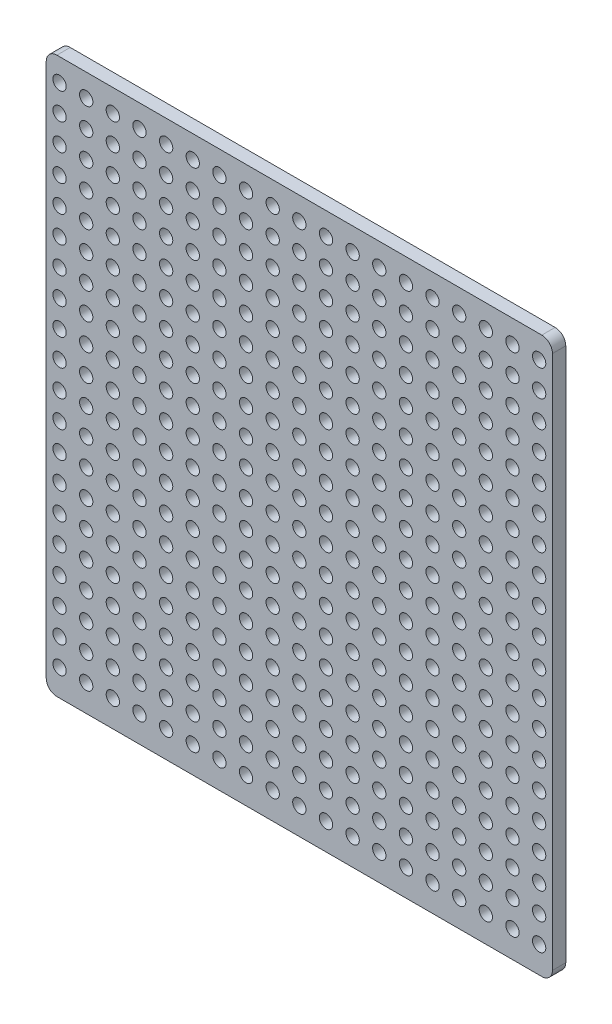
SolidWorks part; units mm, degrees
ref_plane "Front Plane" through (0, 0, 0) normal (0, 0, 1) x (1, 0, 0)
ref_plane "Top Plane" through (0, 0, 0) normal (0, 1, 0) x (1, 0, 0)
ref_plane "Right Plane" through (0, 0, 0) normal (1, 0, 0) x (0, 0, -1)
sketch "Sketch1" plane through (0, 0, 0) normal (0, 0, 1) x (1, 0, 0)
  line L1 (0, 0) -> (190, 0)
  line L2 (0, 0) -> (0, 208.5)
  line L3 (0, 208.5) -> (190, 208.5)
  line L4 (190, 0) -> (190, 208.5)
  circle A1 centre (5, 10) radius 2.5
  circle A2 centre (15, 10) radius 2.5
  circle A3 centre (25, 10) radius 2.5
  circle A4 centre (35, 10) radius 2.5
  circle A5 centre (45, 10) radius 2.5
  circle A6 centre (55, 10) radius 2.5
  circle A7 centre (65, 10) radius 2.5
  circle A8 centre (75, 10) radius 2.5
  circle A9 centre (85, 10) radius 2.5
  circle A10 centre (95, 10) radius 2.5
  circle A11 centre (105, 10) radius 2.5
  circle A12 centre (115, 10) radius 2.5
  circle A13 centre (125, 10) radius 2.5
  circle A14 centre (135, 10) radius 2.5
  circle A15 centre (145, 10) radius 2.5
  circle A16 centre (155, 10) radius 2.5
  circle A17 centre (165, 10) radius 2.5
  circle A18 centre (175, 10) radius 2.5
  circle A19 centre (185, 10) radius 2.5
  circle A21 centre (15, 20) radius 2.5
  circle A22 centre (25, 20) radius 2.5
  circle A23 centre (35, 20) radius 2.5
  circle A24 centre (45, 20) radius 2.5
  circle A25 centre (55, 20) radius 2.5
  circle A26 centre (65, 20) radius 2.5
  circle A27 centre (75, 20) radius 2.5
  circle A28 centre (85, 20) radius 2.5
  circle A29 centre (95, 20) radius 2.5
  circle A30 centre (105, 20) radius 2.5
  circle A31 centre (115, 20) radius 2.5
  circle A32 centre (125, 20) radius 2.5
  circle A33 centre (135, 20) radius 2.5
  circle A34 centre (145, 20) radius 2.5
  circle A35 centre (155, 20) radius 2.5
  circle A36 centre (165, 20) radius 2.5
  circle A37 centre (175, 20) radius 2.5
  circle A38 centre (185, 20) radius 2.5
  circle A40 centre (15, 30) radius 2.5
  circle A41 centre (25, 30) radius 2.5
  circle A42 centre (35, 30) radius 2.5
  circle A43 centre (45, 30) radius 2.5
  circle A44 centre (55, 30) radius 2.5
  circle A45 centre (65, 30) radius 2.5
  circle A46 centre (75, 30) radius 2.5
  circle A47 centre (85, 30) radius 2.5
  circle A48 centre (95, 30) radius 2.5
  circle A49 centre (105, 30) radius 2.5
  circle A50 centre (115, 30) radius 2.5
  circle A51 centre (125, 30) radius 2.5
  circle A52 centre (135, 30) radius 2.5
  circle A53 centre (145, 30) radius 2.5
  circle A54 centre (155, 30) radius 2.5
  circle A55 centre (165, 30) radius 2.5
  circle A56 centre (175, 30) radius 2.5
  circle A57 centre (185, 30) radius 2.5
  circle A59 centre (15, 40) radius 2.5
  circle A60 centre (25, 40) radius 2.5
  circle A61 centre (35, 40) radius 2.5
  circle A62 centre (45, 40) radius 2.5
  circle A63 centre (55, 40) radius 2.5
  circle A64 centre (65, 40) radius 2.5
  circle A65 centre (75, 40) radius 2.5
  circle A66 centre (85, 40) radius 2.5
  circle A67 centre (95, 40) radius 2.5
  circle A68 centre (105, 40) radius 2.5
  circle A69 centre (115, 40) radius 2.5
  circle A70 centre (125, 40) radius 2.5
  circle A71 centre (135, 40) radius 2.5
  circle A72 centre (145, 40) radius 2.5
  circle A73 centre (155, 40) radius 2.5
  circle A74 centre (165, 40) radius 2.5
  circle A75 centre (175, 40) radius 2.5
  circle A76 centre (185, 40) radius 2.5
  circle A78 centre (15, 50) radius 2.5
  circle A79 centre (25, 50) radius 2.5
  circle A80 centre (35, 50) radius 2.5
  circle A81 centre (45, 50) radius 2.5
  circle A82 centre (55, 50) radius 2.5
  circle A83 centre (65, 50) radius 2.5
  circle A84 centre (75, 50) radius 2.5
  circle A85 centre (85, 50) radius 2.5
  circle A86 centre (95, 50) radius 2.5
  circle A87 centre (105, 50) radius 2.5
  circle A88 centre (115, 50) radius 2.5
  circle A89 centre (125, 50) radius 2.5
  circle A90 centre (135, 50) radius 2.5
  circle A91 centre (145, 50) radius 2.5
  circle A92 centre (155, 50) radius 2.5
  circle A93 centre (165, 50) radius 2.5
  circle A94 centre (175, 50) radius 2.5
  circle A95 centre (185, 50) radius 2.5
  circle A97 centre (15, 60) radius 2.5
  circle A98 centre (25, 60) radius 2.5
  circle A99 centre (35, 60) radius 2.5
  circle A100 centre (45, 60) radius 2.5
  circle A101 centre (55, 60) radius 2.5
  circle A102 centre (65, 60) radius 2.5
  circle A103 centre (75, 60) radius 2.5
  circle A104 centre (85, 60) radius 2.5
  circle A105 centre (95, 60) radius 2.5
  circle A106 centre (105, 60) radius 2.5
  circle A107 centre (115, 60) radius 2.5
  circle A108 centre (125, 60) radius 2.5
  circle A109 centre (135, 60) radius 2.5
  circle A110 centre (145, 60) radius 2.5
  circle A111 centre (155, 60) radius 2.5
  circle A112 centre (165, 60) radius 2.5
  circle A113 centre (175, 60) radius 2.5
  circle A114 centre (185, 60) radius 2.5
  circle A116 centre (15, 70) radius 2.5
  circle A117 centre (25, 70) radius 2.5
  circle A118 centre (35, 70) radius 2.5
  circle A119 centre (45, 70) radius 2.5
  circle A120 centre (55, 70) radius 2.5
  circle A121 centre (65, 70) radius 2.5
  circle A122 centre (75, 70) radius 2.5
  circle A123 centre (85, 70) radius 2.5
  circle A124 centre (95, 70) radius 2.5
  circle A125 centre (105, 70) radius 2.5
  circle A126 centre (115, 70) radius 2.5
  circle A127 centre (125, 70) radius 2.5
  circle A128 centre (135, 70) radius 2.5
  circle A129 centre (145, 70) radius 2.5
  circle A130 centre (155, 70) radius 2.5
  circle A131 centre (165, 70) radius 2.5
  circle A132 centre (175, 70) radius 2.5
  circle A133 centre (185, 70) radius 2.5
  circle A135 centre (15, 80) radius 2.5
  circle A136 centre (25, 80) radius 2.5
  circle A137 centre (35, 80) radius 2.5
  circle A138 centre (45, 80) radius 2.5
  circle A139 centre (55, 80) radius 2.5
  circle A140 centre (65, 80) radius 2.5
  circle A141 centre (75, 80) radius 2.5
  circle A142 centre (85, 80) radius 2.5
  circle A143 centre (95, 80) radius 2.5
  circle A144 centre (105, 80) radius 2.5
  circle A145 centre (115, 80) radius 2.5
  circle A146 centre (125, 80) radius 2.5
  circle A147 centre (135, 80) radius 2.5
  circle A148 centre (145, 80) radius 2.5
  circle A149 centre (155, 80) radius 2.5
  circle A150 centre (165, 80) radius 2.5
  circle A151 centre (175, 80) radius 2.5
  circle A152 centre (185, 80) radius 2.5
  circle A154 centre (15, 90) radius 2.5
  circle A155 centre (25, 90) radius 2.5
  circle A156 centre (35, 90) radius 2.5
  circle A157 centre (45, 90) radius 2.5
  circle A158 centre (55, 90) radius 2.5
  circle A159 centre (65, 90) radius 2.5
  circle A160 centre (75, 90) radius 2.5
  circle A161 centre (85, 90) radius 2.5
  circle A162 centre (95, 90) radius 2.5
  circle A163 centre (105, 90) radius 2.5
  circle A164 centre (115, 90) radius 2.5
  circle A165 centre (125, 90) radius 2.5
  circle A166 centre (135, 90) radius 2.5
  circle A167 centre (145, 90) radius 2.5
  circle A168 centre (155, 90) radius 2.5
  circle A169 centre (165, 90) radius 2.5
  circle A170 centre (175, 90) radius 2.5
  circle A171 centre (185, 90) radius 2.5
  circle A173 centre (15, 100) radius 2.5
  circle A174 centre (25, 100) radius 2.5
  circle A175 centre (35, 100) radius 2.5
  circle A176 centre (45, 100) radius 2.5
  circle A177 centre (55, 100) radius 2.5
  circle A178 centre (65, 100) radius 2.5
  circle A179 centre (75, 100) radius 2.5
  circle A180 centre (85, 100) radius 2.5
  circle A181 centre (95, 100) radius 2.5
  circle A182 centre (105, 100) radius 2.5
  circle A183 centre (115, 100) radius 2.5
  circle A184 centre (125, 100) radius 2.5
  circle A185 centre (135, 100) radius 2.5
  circle A186 centre (145, 100) radius 2.5
  circle A187 centre (155, 100) radius 2.5
  circle A188 centre (165, 100) radius 2.5
  circle A189 centre (175, 100) radius 2.5
  circle A190 centre (185, 100) radius 2.5
  circle A192 centre (15, 110) radius 2.5
  circle A193 centre (25, 110) radius 2.5
  circle A194 centre (35, 110) radius 2.5
  circle A195 centre (45, 110) radius 2.5
  circle A196 centre (55, 110) radius 2.5
  circle A197 centre (65, 110) radius 2.5
  circle A198 centre (75, 110) radius 2.5
  circle A199 centre (85, 110) radius 2.5
  circle A200 centre (95, 110) radius 2.5
  circle A201 centre (105, 110) radius 2.5
  circle A202 centre (115, 110) radius 2.5
  circle A203 centre (125, 110) radius 2.5
  circle A204 centre (135, 110) radius 2.5
  circle A205 centre (145, 110) radius 2.5
  circle A206 centre (155, 110) radius 2.5
  circle A207 centre (165, 110) radius 2.5
  circle A208 centre (175, 110) radius 2.5
  circle A209 centre (185, 110) radius 2.5
  circle A211 centre (15, 120) radius 2.5
  circle A212 centre (25, 120) radius 2.5
  circle A213 centre (35, 120) radius 2.5
  circle A214 centre (45, 120) radius 2.5
  circle A215 centre (55, 120) radius 2.5
  circle A216 centre (65, 120) radius 2.5
  circle A217 centre (75, 120) radius 2.5
  circle A218 centre (85, 120) radius 2.5
  circle A219 centre (95, 120) radius 2.5
  circle A220 centre (105, 120) radius 2.5
  circle A221 centre (115, 120) radius 2.5
  circle A222 centre (125, 120) radius 2.5
  circle A223 centre (135, 120) radius 2.5
  circle A224 centre (145, 120) radius 2.5
  circle A225 centre (155, 120) radius 2.5
  circle A226 centre (165, 120) radius 2.5
  circle A227 centre (175, 120) radius 2.5
  circle A228 centre (185, 120) radius 2.5
  circle A230 centre (15, 130) radius 2.5
  circle A231 centre (25, 130) radius 2.5
  circle A232 centre (35, 130) radius 2.5
  circle A233 centre (45, 130) radius 2.5
  circle A234 centre (55, 130) radius 2.5
  circle A235 centre (65, 130) radius 2.5
  circle A236 centre (75, 130) radius 2.5
  circle A237 centre (85, 130) radius 2.5
  circle A238 centre (95, 130) radius 2.5
  circle A239 centre (105, 130) radius 2.5
  circle A240 centre (115, 130) radius 2.5
  circle A241 centre (125, 130) radius 2.5
  circle A242 centre (135, 130) radius 2.5
  circle A243 centre (145, 130) radius 2.5
  circle A244 centre (155, 130) radius 2.5
  circle A245 centre (165, 130) radius 2.5
  circle A246 centre (175, 130) radius 2.5
  circle A247 centre (185, 130) radius 2.5
  circle A249 centre (15, 140) radius 2.5
  circle A250 centre (25, 140) radius 2.5
  circle A251 centre (35, 140) radius 2.5
  circle A252 centre (45, 140) radius 2.5
  circle A253 centre (55, 140) radius 2.5
  circle A254 centre (65, 140) radius 2.5
  circle A255 centre (75, 140) radius 2.5
  circle A256 centre (85, 140) radius 2.5
  circle A257 centre (95, 140) radius 2.5
  circle A258 centre (105, 140) radius 2.5
  circle A259 centre (115, 140) radius 2.5
  circle A260 centre (125, 140) radius 2.5
  circle A261 centre (135, 140) radius 2.5
  circle A262 centre (145, 140) radius 2.5
  circle A263 centre (155, 140) radius 2.5
  circle A264 centre (165, 140) radius 2.5
  circle A265 centre (175, 140) radius 2.5
  circle A266 centre (185, 140) radius 2.5
  circle A268 centre (15, 150) radius 2.5
  circle A269 centre (25, 150) radius 2.5
  circle A270 centre (35, 150) radius 2.5
  circle A271 centre (45, 150) radius 2.5
  circle A272 centre (55, 150) radius 2.5
  circle A273 centre (65, 150) radius 2.5
  circle A274 centre (75, 150) radius 2.5
  circle A275 centre (85, 150) radius 2.5
  circle A276 centre (95, 150) radius 2.5
  circle A277 centre (105, 150) radius 2.5
  circle A278 centre (115, 150) radius 2.5
  circle A279 centre (125, 150) radius 2.5
  circle A280 centre (135, 150) radius 2.5
  circle A281 centre (145, 150) radius 2.5
  circle A282 centre (155, 150) radius 2.5
  circle A283 centre (165, 150) radius 2.5
  circle A284 centre (175, 150) radius 2.5
  circle A285 centre (185, 150) radius 2.5
  circle A287 centre (15, 160) radius 2.5
  circle A288 centre (25, 160) radius 2.5
  circle A289 centre (35, 160) radius 2.5
  circle A290 centre (45, 160) radius 2.5
  circle A291 centre (55, 160) radius 2.5
  circle A292 centre (65, 160) radius 2.5
  circle A293 centre (75, 160) radius 2.5
  circle A294 centre (85, 160) radius 2.5
  circle A295 centre (95, 160) radius 2.5
  circle A296 centre (105, 160) radius 2.5
  circle A297 centre (115, 160) radius 2.5
  circle A298 centre (125, 160) radius 2.5
  circle A299 centre (135, 160) radius 2.5
  circle A300 centre (145, 160) radius 2.5
  circle A301 centre (155, 160) radius 2.5
  circle A302 centre (165, 160) radius 2.5
  circle A303 centre (175, 160) radius 2.5
  circle A304 centre (185, 160) radius 2.5
  circle A306 centre (15, 170) radius 2.5
  circle A307 centre (25, 170) radius 2.5
  circle A308 centre (35, 170) radius 2.5
  circle A309 centre (45, 170) radius 2.5
  circle A310 centre (55, 170) radius 2.5
  circle A311 centre (65, 170) radius 2.5
  circle A312 centre (75, 170) radius 2.5
  circle A313 centre (85, 170) radius 2.5
  circle A314 centre (95, 170) radius 2.5
  circle A315 centre (105, 170) radius 2.5
  circle A316 centre (115, 170) radius 2.5
  circle A317 centre (125, 170) radius 2.5
  circle A318 centre (135, 170) radius 2.5
  circle A319 centre (145, 170) radius 2.5
  circle A320 centre (155, 170) radius 2.5
  circle A321 centre (165, 170) radius 2.5
  circle A322 centre (175, 170) radius 2.5
  circle A323 centre (185, 170) radius 2.5
  circle A325 centre (15, 180) radius 2.5
  circle A326 centre (25, 180) radius 2.5
  circle A327 centre (35, 180) radius 2.5
  circle A328 centre (45, 180) radius 2.5
  circle A329 centre (55, 180) radius 2.5
  circle A330 centre (65, 180) radius 2.5
  circle A331 centre (75, 180) radius 2.5
  circle A332 centre (85, 180) radius 2.5
  circle A333 centre (95, 180) radius 2.5
  circle A334 centre (105, 180) radius 2.5
  circle A335 centre (115, 180) radius 2.5
  circle A336 centre (125, 180) radius 2.5
  circle A337 centre (135, 180) radius 2.5
  circle A338 centre (145, 180) radius 2.5
  circle A339 centre (155, 180) radius 2.5
  circle A340 centre (165, 180) radius 2.5
  circle A341 centre (175, 180) radius 2.5
  circle A342 centre (185, 180) radius 2.5
  circle A344 centre (15, 190) radius 2.5
  circle A345 centre (25, 190) radius 2.5
  circle A346 centre (35, 190) radius 2.5
  circle A347 centre (45, 190) radius 2.5
  circle A348 centre (55, 190) radius 2.5
  circle A349 centre (65, 190) radius 2.5
  circle A350 centre (75, 190) radius 2.5
  circle A351 centre (85, 190) radius 2.5
  circle A352 centre (95, 190) radius 2.5
  circle A353 centre (105, 190) radius 2.5
  circle A354 centre (115, 190) radius 2.5
  circle A355 centre (125, 190) radius 2.5
  circle A356 centre (135, 190) radius 2.5
  circle A357 centre (145, 190) radius 2.5
  circle A358 centre (155, 190) radius 2.5
  circle A359 centre (165, 190) radius 2.5
  circle A360 centre (175, 190) radius 2.5
  circle A361 centre (185, 190) radius 2.5
  circle A363 centre (15, 200) radius 2.5
  circle A364 centre (25, 200) radius 2.5
  circle A365 centre (35, 200) radius 2.5
  circle A366 centre (45, 200) radius 2.5
  circle A367 centre (55, 200) radius 2.5
  circle A368 centre (65, 200) radius 2.5
  circle A369 centre (75, 200) radius 2.5
  circle A370 centre (85, 200) radius 2.5
  circle A371 centre (95, 200) radius 2.5
  circle A372 centre (105, 200) radius 2.5
  circle A373 centre (115, 200) radius 2.5
  circle A374 centre (125, 200) radius 2.5
  circle A375 centre (135, 200) radius 2.5
  circle A376 centre (145, 200) radius 2.5
  circle A377 centre (155, 200) radius 2.5
  circle A378 centre (165, 200) radius 2.5
  circle A379 centre (175, 200) radius 2.5
  circle A380 centre (185, 200) radius 2.5
  circle A382 centre (5, 20) radius 2.5
  circle A383 centre (5, 30) radius 2.5
  circle A384 centre (5, 40) radius 2.5
  circle A385 centre (5, 50) radius 2.5
  circle A386 centre (5, 60) radius 2.5
  circle A387 centre (5, 70) radius 2.5
  circle A388 centre (5, 80) radius 2.5
  circle A389 centre (5, 90) radius 2.5
  circle A390 centre (5, 100) radius 2.5
  circle A391 centre (5, 110) radius 2.5
  circle A392 centre (5, 120) radius 2.5
  circle A393 centre (5, 130) radius 2.5
  circle A394 centre (5, 140) radius 2.5
  circle A395 centre (5, 150) radius 2.5
  circle A396 centre (5, 160) radius 2.5
  circle A397 centre (5, 170) radius 2.5
  circle A398 centre (5, 180) radius 2.5
  circle A399 centre (5, 190) radius 2.5
  circle A400 centre (5, 200) radius 2.5
  dimension "D1" = 190
  dimension "D3" = 5
  dimension "D2" = 208.5
  dimension "D4" = 10
  dimension "D5" = 5
  dimension "D6" = 19
  dimension "D7" = 20
extrude "Boss-Extrude1" add sketch "Sketch1" along normal blind 5
fillet "Fillet1" radius 4 4 edges at (190, 0, 2.5) (0, 0, 2.5) (0, 208.5, 2.5) (190, 208.5, 2.5)
